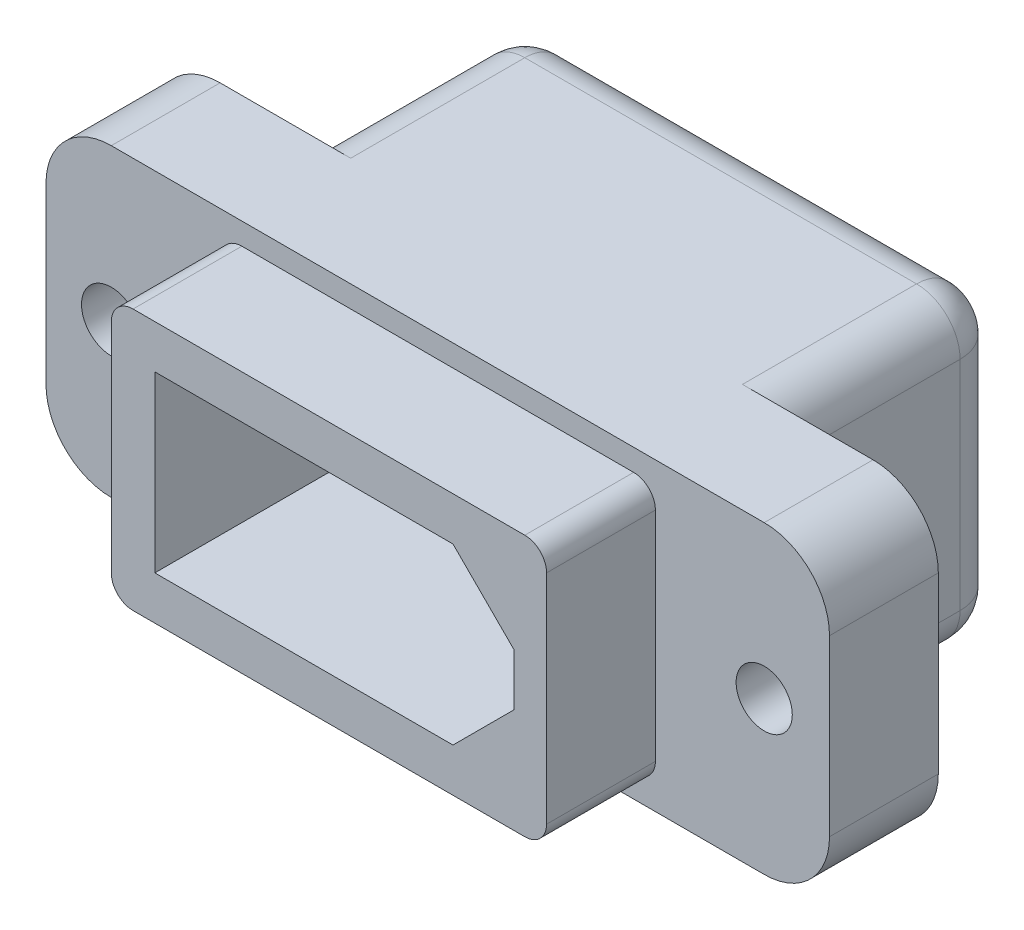
SolidWorks part; units mm, degrees
ref_plane "Спереди" through (0, 0, 0) normal (0, 0, 1) x (1, 0, 0)
ref_plane "Сверху" through (0, 0, 0) normal (0, 1, 0) x (1, 0, 0)
ref_plane "Справа" through (0, 0, 0) normal (1, 0, 0) x (0, 0, -1)
other "Configuration Table"
sketch "Эскиз1" plane through (0, 0, 0) normal (0, 0, 1) x (1, 0, 0)
  line L0 (13.7, 0) -> (16.5, -2.8)
  line L1 (0, 0) -> (13.7, 0)
  line L2 (0, 0) -> (0, -8)
  line L3 (0, -8) -> (13.7, -8)
  line L4 (16.5, -2.8) -> (16.5, -5.2)
  line L5 (8, 4.3172) -> (8, -12.6531) construction
  line L6 (16.5, -5.2) -> (13.7, -8)
  line L7 (-10, 3) -> (26, 3)
  line L8 (-10, 3) -> (-10, -11)
  line L9 (-10, -11) -> (26, -11)
  line L10 (26, 3) -> (26, -11)
  line L11 (-1.1105, -4) -> (-14.755, -4) construction
  circle A0 centre (-7, -4) radius 1.3686
  circle A1 centre (23, -4) radius 1.2907
  dimension "D1" = 3
  dimension "D2" = 3
  dimension "D3" = 45
  dimension "D4" = 18
  dimension "D5" = 8
  dimension "D6" = 45
  dimension "D7" = 18
  dimension "D8" = 15
  dimension "D9" = 15
extrude "Бобышка-Вытянуть1" add sketch "Эскиз1" along normal blind 5
sketch "Эскиз2" plane through (0, 0, 0) normal (0, 0, -1) x (-1, 0, 0)
  line L0 (-26, 3) -> (10, 3) construction
  line L1 (-19, 3) -> (3, 3)
  line L2 (-19, 3) -> (-19, -11)
  line L3 (-19, -11) -> (3, -11)
  line L4 (3, 3) -> (3, -11)
  line L5 (10, -11) -> (-26, -11) construction
  line L6 (-26, -11) -> (-26, 3) construction
  line L7 (10, 3) -> (10, -11) construction
  line L8 (-16.5, -2.8) -> (-13.7, 0)
  line L9 (-13.7, 0) -> (0, 0)
  line L10 (0, 0) -> (0, -8)
  line L11 (0, -8) -> (-13.7, -8)
  line L12 (-13.7, -8) -> (-16.5, -5.2)
  line L13 (-16.5, -5.2) -> (-16.5, -2.8)
  dimension "D1" = 7
  dimension "D2" = 7
extrude "Бобышка-Вытянуть2" add sketch "Эскиз2" along normal blind 6
sketch "Эскиз3" plane through (0, 0, -6) normal (0, 0, -1) x (-1, 0, 0)
  line L1 (-19, 3) -> (3, 3)
  line L2 (-19, 3) -> (-19, -11)
  line L3 (-19, -11) -> (3, -11)
  line L4 (3, 3) -> (3, -11)
  line L5 (0, -8) -> (0, 0) construction
  line L6 (-15.5, -1) -> (-1, -1)
  line L7 (-15.5, -1) -> (-15.5, -7)
  line L8 (-15.5, -7) -> (-1, -7)
  line L9 (-1, -1) -> (-1, -7)
  line L10 (0, 0) -> (-13.7, 0) construction
  line L11 (-16.5, -2.8) -> (-16.5, -5.2) construction
  line L12 (-13.7, -8) -> (0, -8) construction
  dimension "D1" = 1
  dimension "D2" = 1
  dimension "D3" = 1
  dimension "D4" = 1
extrude "Бобышка-Вытянуть3" add sketch "Эскиз3" along normal blind 4
fillet "Скругление1" radius 3 4 edges at (26, 3, 2.5) (26, -11, 2.5) (-10, -11, 2.5) (-10, 3, 2.5)
fillet "Скругление2" radius 2 8 edges at (15.5, -1, -8) (15.5, -7, -8) (1, -7, -8) (1, -1, -8) (-3, -11, -5) (-3, 3, -5) (19, -11, -5) (19, 3, -5)
fillet "Скругление3" radius 2 16 edges at (1.5858, -6.4142, -10) (1, -4, -10) (1.5858, -1.5858, -10) (8.25, -1, -10) (14.9142, -1.5858, -10) (15.5, -4, -10) (14.9142, -6.4142, -10) (8.25, -7, -10) (18.4142, -10.4142, -10) (19, -4, -10) (18.4142, 2.4142, -10) (8, 3, -10) (-2.4142, 2.4142, -10) (-3, -4, -10) (-2.4142, -10.4142, -10) (8, -11, -10)
sketch "Эскиз4" plane through (0, 0, 5) normal (0, 0, 1) x (1, 0, 0)
  line L0 (13.7, 0) -> (0, 0) construction
  line L1 (-2, 2) -> (18, 2)
  line L2 (-2, 2) -> (-2, -10)
  line L3 (-2, -10) -> (18, -10)
  line L4 (18, 2) -> (18, -10)
  line L5 (0, 0) -> (0, -8) construction
  line L6 (0, 0) -> (13.7, 0)
  line L7 (13.7, 0) -> (16.5, -2.8)
  line L8 (16.5, -2.8) -> (16.5, -5.2)
  line L9 (16.5, -5.2) -> (13.7, -8)
  line L10 (13.7, -8) -> (0, -8)
  line L11 (0, -8) -> (0, 0)
  circle A0 centre (-7, -4) radius 1.3686 construction
  circle A1 centre (23, -4) radius 1.2907 construction
  dimension "D1" = 12
  dimension "D2" = 2
  dimension "D3" = 2
  dimension "D4" = 20
extrude "Бобышка-Вытянуть4" add sketch "Эскиз4" along normal blind 5
fillet "Скругление4" radius 1 4 edges at (-2, 2, 7.5) (-2, -10, 7.5) (18, -10, 7.5) (18, 2, 7.5)
